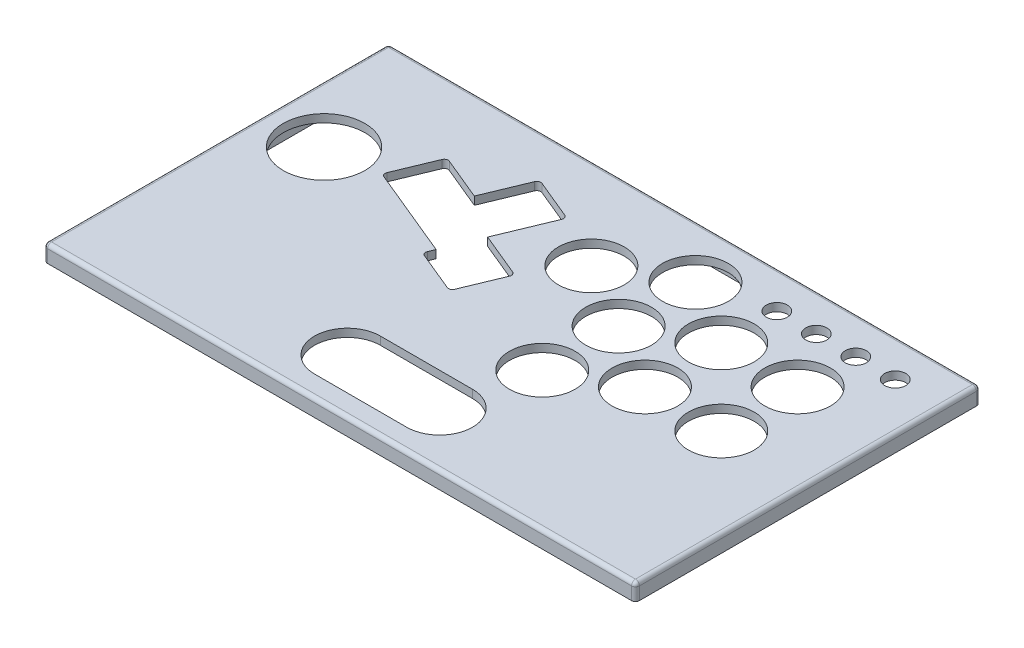
SolidWorks part; units mm, degrees
ref_plane "Front Plane" through (0, 0, 0) normal (0, 0, 1) x (1, 0, 0)
ref_plane "Top Plane" through (0, 0, 0) normal (0, 1, 0) x (1, 0, 0)
ref_plane "Right Plane" through (0, 0, 0) normal (1, 0, 0) x (0, 0, -1)
sketch "Button Cutouts" plane through (0, 0, 0) normal (0, 1, 0) x (1, 0, 0)
  line L0 (24.5, 61) -> (24.5, 32) construction
  line L1 (298.8548, 529.5585) -> (1494.2739, 529.5585) construction
  line L12 (-36.2591, 48.1292) -> (-29.3708, 64.7591) construction
  line L20 (49.5, 75) -> (49.5, 46) construction
  line L21 (78.5, 75) -> (78.5, 46) construction
  line L22 (17.5, 0) -> (-17.5, 0) construction
  line L28 (-36.2591, 48.1292) -> (-19.6292, 41.2409) construction
  line L29 (17.5, -12.5) -> (-17.5, -12.5)
  line L30 (17.5, 12.5) -> (-17.5, 12.5)
  line L31 (24.6803, 89.9994) -> (49.5, 75) construction
  line L32 (24.6803, 89.9994) -> (24.5, 61) construction
  line L33 (-0.5241, 75.6559) -> (24.6803, 89.9994) construction
  line L34 (-0.5241, 75.6559) -> (24.5, 61) construction
  line L48 (-29.3708, 64.7591) -> (-12.7409, 57.8708) construction
  line L49 (-19.6292, 41.2409) -> (-12.7409, 57.8708) construction
  line L50 (-36.2591, 48.1292) -> (-12.7409, 57.8708) construction
  line L51 (-29.3708, 64.7591) -> (-19.6292, 41.2409) construction
  line L52 (-35.6984, 52.2266) -> (-28.8101, 68.8564) construction
  line L53 (-35.6984, 52.2266) -> (-52.3282, 59.1149) construction
  line L54 (-28.8101, 68.8564) -> (-45.4399, 75.7447) construction
  line L55 (-52.3282, 59.1149) -> (-45.4399, 75.7447) construction
  line L56 (-35.6984, 52.2266) -> (-45.4399, 75.7447) construction
  line L57 (-28.8101, 68.8564) -> (-52.3282, 59.1149) construction
  line L58 (-69.9281, 66.405) -> (-63.0398, 83.0348) construction
  line L59 (-69.9281, 66.405) -> (-53.2983, 59.5167) construction
  line L60 (-63.0398, 83.0348) -> (-46.41, 76.1465) construction
  line L61 (-53.2983, 59.5167) -> (-46.41, 76.1465) construction
  line L62 (-69.9281, 66.405) -> (-46.41, 76.1465) construction
  line L63 (-63.0398, 83.0348) -> (-53.2983, 59.5167) construction
  line L64 (-40.5692, 63.9856) -> (-22.9693, 56.6955) construction
  line L65 (-40.5692, 63.9856) -> (-58.1691, 71.2758) construction
  line L66 (-45.0381, 76.7148) -> (-38.1498, 93.3446) construction
  line L67 (-45.0381, 76.7148) -> (-28.4083, 69.8265) construction
  line L68 (-38.1498, 93.3446) -> (-21.52, 86.4563) construction
  line L69 (-28.4083, 69.8265) -> (-21.52, 86.4563) construction
  line L70 (-45.0381, 76.7148) -> (-21.52, 86.4563) construction
  line L71 (-38.1498, 93.3446) -> (-28.4083, 69.8265) construction
  line L72 (-40.5692, 63.9856) -> (-33.2791, 81.5855) construction
  line L73 (-24.5, 53) -> (-22.9693, 56.6955) construction
  line L74 (-58.1691, 71.2758) -> (-65.4592, 53.6759) construction
  line L75 (-65.4592, 53.6759) -> (-90.4039, 64.0083) construction
  line L76 (-70.5814, 66.1344) -> (-63.3104, 83.6881)
  line L77 (-63.3104, 83.6881) -> (-45.7105, 76.398)
  line L78 (-45.7105, 76.398) -> (-38.4204, 93.9979)
  line L79 (-38.4204, 93.9979) -> (-20.8667, 86.7269)
  line L80 (-20.8667, 86.7269) -> (-29.6876, 65.4315)
  line L81 (-29.6876, 65.4315) -> (-12.0877, 58.1414)
  line L82 (-12.0877, 58.1414) -> (-19.3586, 40.5877)
  line L83 (-19.3586, 40.5877) -> (-36.9123, 47.8586)
  line L84 (-36.9123, 47.8586) -> (-35.3816, 51.5542)
  line L85 (-35.3816, 51.5542) -> (-70.5814, 66.1344)
  line L86 (-66.484, 74.7199) -> (-66.9459, 74.9112) construction
  line L87 (-29.6436, 90.3624) -> (-29.8349, 89.9005) construction
  line L88 (-16.1851, 49.5558) -> (-15.7231, 49.3645) construction
  line L89 (-33.2791, 140.3317) -> (-33.2791, 81.5855) construction
  circle A0 centre (24.5, 32) radius 12.5
  circle A1 centre (24.5, 61) radius 12.5
  circle A2 centre (49.5, 46) radius 12.5
  circle A3 centre (49.5, 75) radius 12.5
  circle A4 centre (78.5, 75) radius 12.5
  circle A5 centre (78.5, 46) radius 12.5
  arc A8 (17.5, -12.5) -> (17.5, 12.5) centre (17.5, 0) ccw
  arc A9 (-17.5, 12.5) -> (-17.5, -12.5) centre (-17.5, 0) ccw
  circle A10 centre (-90.4039, 64.0083) radius 15.5
  circle A11 centre (24.6803, 89.9994) radius 12.5
  circle A12 centre (-0.5241, 75.6559) radius 12.5
  point P1 (-24.5, 53)
  point P5 (-40.5692, 63.9856)
  point P6 (-58.1691, 71.2758)
  point P37 (0, 0)
  point P45 (-33.2791, 81.5855)
  point P54 (-30, 0)
  point P55 (30, 0)
  dimension "D2" = 25
  dimension "D12" = 12.5
  dimension "D18" = 31
  dimension "D25" = 22.5
  dimension "D1" = 29
  dimension "D3" = 25
  dimension "D4" = 29
  dimension "D5" = 14
  dimension "D6" = 18
  dimension "D7" = 19.05
  dimension "D8" = 53
  dimension "D9" = 7
  dimension "D10" = 4
  dimension "D11" = 27
  dimension "D13" = 32
  dimension "D14" = 7
  dimension "D15" = 19.05
  dimension "D16" = 0.5
  dimension "D17" = 60
  dimension "D19" = 0.5
  dimension "D20" = 0.5
  dimension "D21" = 29
  dimension "D22" = 29
  dimension "D23" = 0.5
  dimension "D24" = 0.5
sketch "Sketch2" plane through (0, 0, 0) normal (0, 1, 0) x (1, 0, 0)
  line L0 (-105.9039, 64.0083) -> (-112.4039, 64.0083) construction
  line L1 (-112.4039, 110.4994) -> (112.4039, 110.4994)
  line L2 (-112.4039, 110.4994) -> (-112.4039, -20.5)
  line L3 (-112.4039, -20.5) -> (112.4039, -20.5)
  line L4 (112.4039, 110.4994) -> (112.4039, -20.5)
  line L5 (24.6803, 102.4994) -> (24.6803, 110.4994) construction
  line L6 (0, -12.5) -> (0, -20.5) construction
  line L7 (17.5, -12.5) -> (-17.5, -12.5) construction
  circle A0 centre (-90.4039, 64.0083) radius 15.5 construction
  circle A2 centre (24.6803, 89.9994) radius 12.5 construction
  point P4 (0, -20.5)
  dimension "D2" = 6.5
  dimension "D1" = 8
  dimension "D3" = 8
extrude "top plate" add sketch "Sketch2" along normal blind 6.35
extrude "primary button cutouts" cut sketch "Button Cutouts" along normal up to next
fillet "Fillet1" radius 1.5 7 edges at (-20.8667, 3.175, -86.7269) (-12.0877, 3.175, -58.1414) (-19.3586, 3.175, -40.5877) (-36.9123, 3.175, -47.8586) (-70.5814, 3.175, -66.1344) (-63.3104, 3.175, -83.6881) (-38.4204, 3.175, -93.9979)
sketch "Sketch3" plane through (0, 6.35, 0) normal (0, 1, 0) x (1, 0, 0)
  line L0 (45.0961, 96) -> (54.0961, 96) construction
  line L1 (60.0961, 96) -> (69.0961, 96) construction
  line L2 (75.0961, 96) -> (84.0961, 96) construction
  line L3 (90.0961, 96) -> (99.0961, 96) construction
  circle A10 centre (49.5961, 96) radius 4
  circle A11 centre (64.5961, 96) radius 4
  circle A12 centre (79.5961, 96) radius 4
  circle A13 centre (94.5961, 96) radius 4
  dimension "D1" = 8
extrude "extra buttons" cut sketch "Sketch3" against normal up to next
sketch "Sketch4" plane through (0, 0, 0) normal (0, -1, 0) x (1, 0, 0)
  line L0 (112.4039, 20.5) -> (112.4039, -110.4994) construction
  line L1 (-106.4039, 14.5) -> (106.4039, 14.5)
  line L2 (-106.4039, 14.5) -> (-106.4039, -104.4994)
  line L3 (-106.4039, -104.4994) -> (106.4039, -104.4994)
  line L4 (106.4039, 14.5) -> (106.4039, -104.4994)
  line L5 (-112.4039, 20.5) -> (112.4039, 20.5) construction
  line L6 (112.4039, -110.4994) -> (-112.4039, -110.4994) construction
  line L7 (-112.4039, -110.4994) -> (-112.4039, 20.5) construction
  dimension "D1" = 6
  dimension "D2" = 6
  dimension "D3" = 6
  dimension "D4" = 6
extrude "Cut-Extrude2" cut sketch "Sketch4" against normal blind 3.3
fillet "Fillet2" radius 1.5 8 edges at (112.4039, 3.175, -110.4994) (-112.4039, 3.175, -110.4994) (-112.4039, 3.175, 20.5) (112.4039, 3.175, 20.5) (112.4039, 6.35, -44.9997) (0, 6.35, -110.4994) (0, 6.35, 20.5) (-112.4039, 6.35, -44.9997)
sketch "Sketch5" plane through (0, 0, 0) normal (0, -1, 0) x (1, 0, 0)
  line L0 (110.9039, -110.4994) -> (-110.9039, -110.4994) construction
  line L1 (-82.9087, -104.4994) -> (-47.9087, -104.4994)
  line L2 (-82.9087, -104.4994) -> (-82.9087, -110.4994)
  line L3 (-82.9087, -110.4994) -> (-47.9087, -110.4994)
  line L4 (-47.9087, -104.4994) -> (-47.9087, -110.4994)
  line L5 (-47.9087, -104.4994) -> (-47.9087, -110.4994) construction
extrude "Cut-Extrude3" cut sketch "Sketch5" against normal blind 3
hole_wizard "Tap Drill for M3x0.5 Tap1" positions "3DSketch1" profile "Sketch6" hole size "M3x0.5" standard "ANSI Metric"
sketch3d "3DSketch1"
  line L0 (-108.4039, 0, 16.5) -> (-108.4039, 0, 20.5) construction
  line L1 (-110.9039, 0, 20.5) -> (110.9039, 0, 20.5) construction
  line L3 (-108.4039, 0, 16.5) -> (-112.4039, 0, 16.5)
  line L4 (-112.4039, 0, -108.9994) -> (-112.4039, 0, 19) construction
  line L6 (108.4039, 0, -106.4994) -> (112.4039, 0, -106.4994)
  line L7 (112.4039, 0, 19) -> (112.4039, 0, -108.9994) construction
  line L9 (108.4039, 0, -106.4994) -> (108.4039, 0, -110.4994)
  line L10 (110.9039, 0, -110.4994) -> (-47.9087, 0, -110.4994) construction
  point P0 (-108.4039, 0, 16.5)
  point P2 (-108.4039, 0, -106.4994)
  point P4 (108.4039, 0, -106.4994)
  point P6 (108.4039, 0, 16.5)
  dimension "D1" = 4
sketch "Sketch6" plane through (-108.4039, 0, 16.5) normal (1, 0, 0) x (0, 0, -1)
  line L0 (0, 0) -> (0, 4.7511)
  line L1 (0, 4.7511) -> (1.25, 4)
  line L2 (1.25, 4) -> (1.25, 0)
  line L5 (1.25, 0) -> (0, 0)
  line L10 (0, 4.7511) -> (-1.25, 4) construction
  line L11 (0, -6.35) -> (0, 107.95) construction
  dimension "Hole Dia." = 2.5
  dimension "Hole Depth" = 4
  dimension "Drill Angle" = 118
